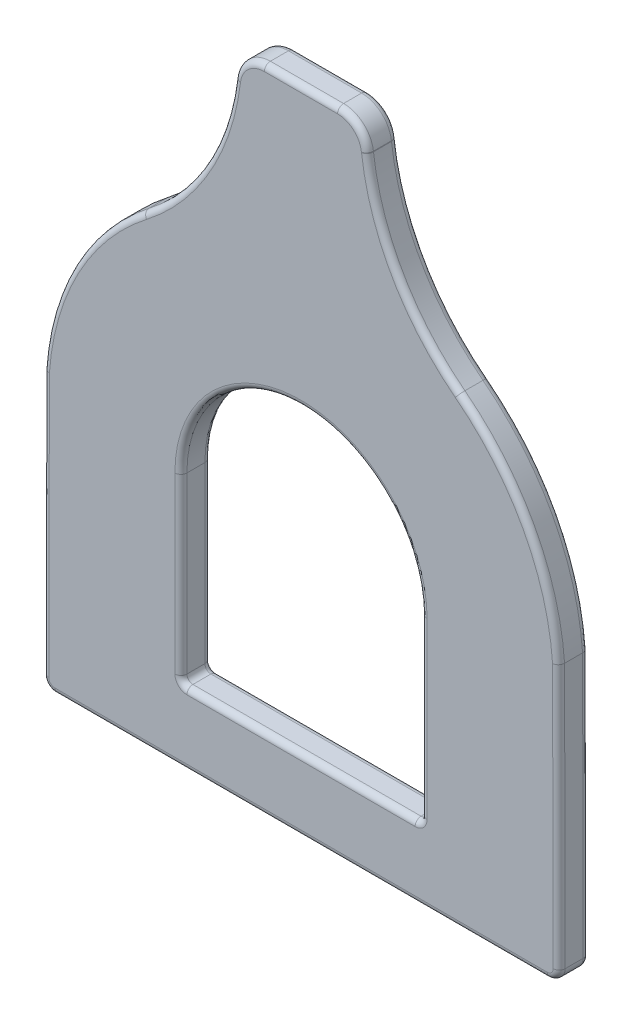
SolidWorks part; units mm, degrees
ref_plane "Front Plane" through (0, 0, 0) normal (0, 0, 1) x (1, 0, 0)
ref_plane "Top Plane" through (0, 0, 0) normal (0, 1, 0) x (1, 0, 0)
ref_plane "Right Plane" through (0, 0, 0) normal (1, 0, 0) x (0, 0, -1)
sketch "Sketch2" plane through (0, 0, 0) normal (0, 0, 1) x (1, 0, 0)
  line L0 (-21.4476, 11.4999) -> (-21.5, -11.5)
  line L5 (0, 42.6667) -> (0, -17.9649) construction
  line L6 (-3.0476, 42.6667) -> (3.0476, 42.6667)
  line L7 (21.5, -11.5) -> (-21.5, -11.5)
  line L8 (21.4476, 11.4999) -> (21.5, -11.5)
  line L9 (5.5295, 40.4672) -> (5.5348, 40.4229)
  line L10 (-5.5295, 40.4672) -> (-5.5348, 40.4229)
  arc A1 (21.4476, 11.4999) -> (13.1538, 27.0067) centre (0, 10) ccw
  arc A2 (-13.1538, 27.0067) -> (-21.4476, 11.4999) centre (0, 10) ccw
  arc A3 (5.5348, 40.4229) -> (13.1538, 27.0067) centre (25.3898, 42.8269) ccw
  arc A4 (-5.5348, 40.4229) -> (-13.1538, 27.0067) centre (-25.3898, 42.8269) cw
  arc A5 (-5.5295, 40.4672) -> (-3.0476, 42.6667) centre (-3.0476, 40.1667) cw
  arc A6 (3.0476, 42.6667) -> (5.5295, 40.4672) centre (3.0476, 40.1667) cw
  point P0 (0, 0)
  point P15 (6.7467, 30.414)
  point P18 (-6.7467, 30.414)
  point P21 (-5.2632, 42.6667)
  point P24 (5.2632, 42.6667)
  dimension "D3" = 20
  dimension "D4" = 2.5
  dimension "D1" = 23
  dimension "D2" = 23
extrude "Boss-Extrude1" add sketch "Sketch2" along normal blind 2.5 contours A4 A2 L0 L7 L8 A1 A3 L9 A6 L6 A5 L10
fillet "Fillet1" radius 1 2 edges at (-21.5, -11.5, 1.25) (21.5, -11.5, 1.25)
fillet "Fillet2" radius 0.5 14 edges at (-18.9586, 20.1401, 2.5) (-7.9985, 32.9505, 2.5) (-5.5322, 40.445, 2.5) (-4.7057, 42.0377, 2.5) (0, 42.6667, 2.5) (4.7057, 42.0377, 2.5) (5.5322, 40.445, 2.5) (7.9985, 32.9505, 2.5) (18.9586, 20.1401, 2.5) (21.4727, 0.5011, 2.5) (21.2056, -11.2063, 2.5) (0, -11.5, 2.5) (-21.2056, -11.2063, 2.5) (-21.4727, 0.5011, 2.5)
fillet "Fillet3" radius 0.5 14 edges at (21.2056, -11.2063, 0) (21.4727, 0.5011, 0) (18.9586, 20.1401, 0) (7.9985, 32.9505, 0) (5.5322, 40.445, 0) (4.7057, 42.0377, 0) (0, 42.6667, 0) (-4.7057, 42.0377, 0) (-5.5322, 40.445, 0) (-7.9985, 32.9505, 0) (-18.9586, 20.1401, 0) (-21.4727, 0.5011, 0) (-21.2056, -11.2063, 0) (0, -11.5, 0)
sketch "Sketch4" plane through (0, 0, 0) normal (0, 0, -1) x (-1, 0, 0)
  line L0 (20.4977, -11.5) -> (-20.4977, -11.5) construction
  line L1 (-10, -5.5) -> (10, -5.5)
  line L2 (-10, -5.5) -> (-10, 9.5)
  line L4 (10, -5.5) -> (10, 9.5)
  line L5 (-10, -5.5) -> (10, 9.5) construction
  line L6 (-10, 9.5) -> (10, -5.5) construction
  arc A0 (-10, 9.5) -> (10, 9.5) centre (0, 9.5) cw
  point P0 (0, 2)
  dimension "D1" = 20
  dimension "D2" = 15
  dimension "D3" = 6
  dimension "D4" = 10
extrude "Cut-Extrude2" cut sketch "Sketch4" against normal blind 2.5
fillet "Fillet4" radius 0.5 10 edges at (-10, 2, 2.5) (0, 19.5, 2.5) (-10, 2, 0) (0, 19.5, 0) (0, -5.5, 2.5) (-10, -5.5, 1.25) (0, -5.5, 0) (10, 2, 2.5) (10, -5.5, 1.25) (10, 2, 0)
